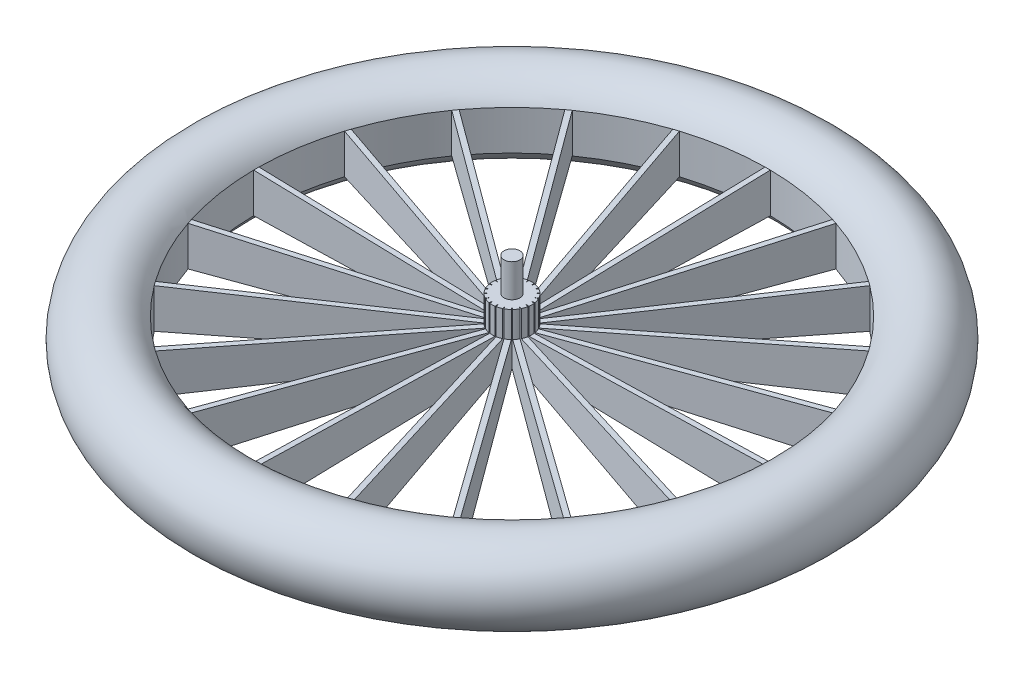
SolidWorks part; units mm, degrees
ref_plane "Plan de face" through (0, 0, 0) normal (0, 0, 1) x (1, 0, 0)
ref_plane "Plan de dessus" through (0, 0, 0) normal (0, 1, 0) x (1, 0, 0)
ref_plane "Plan de droite" through (0, 0, 0) normal (1, 0, 0) x (0, 0, -1)
sketch "Esquisse1" plane through (0, 0, 0) normal (0, 0, 1) x (1, 0, 0)
  line L0 (0, 0) -> (50000, 0) construction
  line L1 (-6, -30) -> (6, -30)
  line L2 (-6, -30) -> (-6, 30)
  line L3 (-6, 30) -> (6, 30)
  line L4 (6, -30) -> (6, 30)
  line L5 (-6, -30) -> (6, 30) construction
  line L6 (-6, 30) -> (6, -30) construction
  line L7 (-194.0192, 15) -> (-6, 10)
  line L8 (-6, -10) -> (6, -10)
  line L9 (-6, -10) -> (-6, 10)
  line L10 (-6, 10) -> (6, 10)
  line L11 (6, -10) -> (6, 10)
  line L12 (-6, -10) -> (6, 10) construction
  line L13 (-6, 10) -> (6, -10) construction
  line L14 (-220, -30) -> (220, -30)
  line L15 (-220, -30) -> (-220, 30)
  line L16 (-220, 30) -> (220, 30)
  line L17 (220, -30) -> (220, 30)
  line L18 (-220, -30) -> (220, 30) construction
  line L19 (-220, 30) -> (220, -30) construction
  line L20 (-245.9808, -15) -> (-194.0192, -15)
  line L21 (-245.9808, -15) -> (-245.9808, 15)
  line L22 (-245.9808, 15) -> (-194.0192, 15)
  line L23 (0, 30) -> (0, -30)
  line L24 (-194.0192, -15) -> (-194.0192, 15)
  line L25 (-15, 30) -> (15, 30)
  line L26 (-15, 30) -> (-15, -30)
  line L27 (-15, -30) -> (15, -30)
  line L28 (15, 30) -> (15, -30)
  line L29 (-15, 30) -> (15, -30) construction
  line L30 (-15, -30) -> (15, 30) construction
  line L31 (-245.9808, -15) -> (-194.0192, 15) construction
  line L32 (-245.9808, 15) -> (-194.0192, -15) construction
  line L33 (-194.0192, -15) -> (-6, -10)
  line L34 (0, 55) -> (0, -55)
  line L35 (-6, -55) -> (6, -55)
  line L36 (-6, -55) -> (-6, 55)
  line L37 (-6, 55) -> (6, 55)
  line L38 (6, -55) -> (6, 55)
  line L39 (-6, -55) -> (6, 55) construction
  line L40 (-6, 55) -> (6, -55) construction
  circle A0 centre (220, 0) radius 30
  circle A1 centre (-220, 0) radius 30
  point P0 (0, 0)
  point P8 (6, 0)
  point P9 (0, 0)
  point P14 (0, 0)
  point P25 (0, 0)
  point P34 (0, 0)
  dimension "D1" = 12
  dimension "D2" = 60
  dimension "D3" = 20
  dimension "D4" = 60
  dimension "D5" = 440
  dimension "D6" = 30
  dimension "D7" = 30
  dimension "D8" = 12
  dimension "D9" = 110
revolve "Révolution1" add sketch "Esquisse1" angle 360 about L23 region at (-10.5177, 0, 0) region at (-10.491, 20.0597, 0) region at (-3, 20, 0) region at (-108.6258, 0, 0) region at (-230.1761, -21.1506, 0) region at (-209.8239, -21.1506, 0) region at (-3, 42.5, 0) region at (-207.0096, 0, 0) region at (-192.4019, 0, 0) region at (-232.9904, 0, 0) region at (-247.5981, 0, 0) region at (-209.8239, 21.1506, 0) region at (-230.1761, 21.1506, 0)
sketch "Esquisse4" plane through (0, 0, 0) normal (0, 1, 0) x (1, 0, 0)
  line L0 (0, 194.0192) -> (0, 15)
  line L1 (0, 15) -> (0, 0)
  line L2 (-2, 194.0192) -> (-2, 15)
  line L3 (-2, 15) -> (-2, 0)
  line L4 (2, 194.0192) -> (2, 15)
  line L5 (2, 15) -> (2, 0)
  line L6 (58.0531, 185.1413) -> (2.7331, 14.8839)
  line L7 (61.8574, 183.9052) -> (6.5374, 13.6478)
  line L8 (2.7331, 14.8839) -> (-1.9021, 0.618)
  line L9 (6.5374, 13.6478) -> (1.9021, -0.618)
  line L10 (112.4236, 158.1404) -> (7.1987, 13.3108)
  line L11 (115.6597, 155.7893) -> (10.4348, 10.9597)
  line L12 (7.1987, 13.3108) -> (-1.618, 1.1756)
  line L13 (10.4348, 10.9597) -> (1.618, -1.1756)
  line L14 (155.7893, 115.6597) -> (10.9597, 10.4348)
  line L15 (158.1404, 112.4236) -> (13.3108, 7.1987)
  line L16 (10.9597, 10.4348) -> (-1.1756, 1.618)
  line L17 (13.3108, 7.1987) -> (1.1756, -1.618)
  line L18 (183.9052, 61.8574) -> (13.6478, 6.5374)
  line L19 (185.1413, 58.0531) -> (14.8839, 2.7331)
  line L20 (13.6478, 6.5374) -> (-0.618, 1.9021)
  line L21 (14.8839, 2.7331) -> (0.618, -1.9021)
  line L22 (194.0192, 2) -> (15, 2)
  line L23 (194.0192, -2) -> (15, -2)
  line L24 (15, 2) -> (0, 2)
  line L25 (15, -2) -> (0, -2)
  line L26 (185.1413, -58.0531) -> (14.8839, -2.7331)
  line L27 (183.9052, -61.8574) -> (13.6478, -6.5374)
  line L28 (14.8839, -2.7331) -> (0.618, 1.9021)
  line L29 (13.6478, -6.5374) -> (-0.618, -1.9021)
  line L30 (158.1404, -112.4236) -> (13.3108, -7.1987)
  line L31 (155.7893, -115.6597) -> (10.9597, -10.4348)
  line L32 (13.3108, -7.1987) -> (1.1756, 1.618)
  line L33 (10.9597, -10.4348) -> (-1.1756, -1.618)
  line L34 (115.6597, -155.7893) -> (10.4348, -10.9597)
  line L35 (112.4236, -158.1404) -> (7.1987, -13.3108)
  line L36 (10.4348, -10.9597) -> (1.618, 1.1756)
  line L37 (7.1987, -13.3108) -> (-1.618, -1.1756)
  line L38 (61.8574, -183.9052) -> (6.5374, -13.6478)
  line L39 (58.0531, -185.1413) -> (2.7331, -14.8839)
  line L40 (6.5374, -13.6478) -> (1.9021, 0.618)
  line L41 (2.7331, -14.8839) -> (-1.9021, -0.618)
  line L42 (2, -194.0192) -> (2, -15)
  line L43 (-2, -194.0192) -> (-2, -15)
  line L44 (2, -15) -> (2, 0)
  line L45 (-2, -15) -> (-2, 0)
  line L46 (-58.0531, -185.1413) -> (-2.7331, -14.8839)
  line L47 (-61.8574, -183.9052) -> (-6.5374, -13.6478)
  line L48 (-2.7331, -14.8839) -> (1.9021, -0.618)
  line L49 (-6.5374, -13.6478) -> (-1.9021, 0.618)
  line L50 (-112.4236, -158.1404) -> (-7.1987, -13.3108)
  line L51 (-115.6597, -155.7893) -> (-10.4348, -10.9597)
  line L52 (-7.1987, -13.3108) -> (1.618, -1.1756)
  line L53 (-10.4348, -10.9597) -> (-1.618, 1.1756)
  line L54 (-155.7893, -115.6597) -> (-10.9597, -10.4348)
  line L55 (-158.1404, -112.4236) -> (-13.3108, -7.1987)
  line L56 (-10.9597, -10.4348) -> (1.1756, -1.618)
  line L57 (-13.3108, -7.1987) -> (-1.1756, 1.618)
  line L58 (-183.9052, -61.8574) -> (-13.6478, -6.5374)
  line L59 (-185.1413, -58.0531) -> (-14.8839, -2.7331)
  line L60 (-13.6478, -6.5374) -> (0.618, -1.9021)
  line L61 (-14.8839, -2.7331) -> (-0.618, 1.9021)
  line L62 (-194.0192, -2) -> (-15, -2)
  line L63 (-194.0192, 2) -> (-15, 2)
  line L64 (-15, -2) -> (0, -2)
  line L65 (-15, 2) -> (0, 2)
  line L66 (-185.1413, 58.0531) -> (-14.8839, 2.7331)
  line L67 (-183.9052, 61.8574) -> (-13.6478, 6.5374)
  line L68 (-14.8839, 2.7331) -> (-0.618, -1.9021)
  line L69 (-13.6478, 6.5374) -> (0.618, 1.9021)
  line L70 (-158.1404, 112.4236) -> (-13.3108, 7.1987)
  line L71 (-155.7893, 115.6597) -> (-10.9597, 10.4348)
  line L72 (-13.3108, 7.1987) -> (-1.1756, -1.618)
  line L73 (-10.9597, 10.4348) -> (1.1756, 1.618)
  line L74 (-115.6597, 155.7893) -> (-10.4348, 10.9597)
  line L75 (-112.4236, 158.1404) -> (-7.1987, 13.3108)
  line L76 (-10.4348, 10.9597) -> (-1.618, -1.1756)
  line L77 (-7.1987, 13.3108) -> (1.618, 1.1756)
  line L78 (-61.8574, 183.9052) -> (-6.5374, 13.6478)
  line L79 (-58.0531, 185.1413) -> (-2.7331, 14.8839)
  line L80 (-6.5374, 13.6478) -> (-1.9021, -0.618)
  line L81 (-2.7331, 14.8839) -> (1.9021, 0.618)
  circle A0 centre (0, 0) radius 15 construction
  circle A1 centre (0, 0) radius 194.0192
  circle A2 centre (0, 0) radius 194.0192
  point P131 (0, 0)
  dimension "D2" = 2
  dimension "D1" = 0
  dimension "D3" = 2
  dimension "D4" = 20
extrude "Enlèv. mat.-Extru.2" cut sketch "Esquisse4" against normal through all both and the other way through all contours L2 A2 L79 L81 L3 | L78 A2 L75 L77 L80 | L74 A2 L71 L73 L76 | L70 A2 L67 L69 L72 | L66 A2 L63 L65 L68 | L62 A2 L59 L61 L64 | L58 A2 L55 L57 L60 | L54 A2 L51 L53 L56 | L50 A2 L47 L49 L52 | L46 A2 L43 L45 L48 | L42 A2 L39 L41 L44 | L38 A2 L35 L37 L40 | L34 A2 L31 L33 L36 | L30 A2 L27 L29 L32 | L26 A2 L23 L25 L28 | L22 A2 L19 L21 L24 | L18 A2 L15 L17 L20 | L14 A2 L11 L13 L16 | L10 A2 L7 L9 L12 | L6 A2 L4 L5 L8 region at (20.8283, 0, -131.5046) region at (-20.8283, 0, -131.5046) region at (60.446, 0, -118.632) region at (-60.446, 0, -118.632) region at (94.1469, 0, -94.1469) region at (-94.1469, 0, -94.1469) region at (118.632, 0, -60.446) region at (-118.632, 0, -60.446) region at (131.5046, 0, -20.8283) region at (-131.5046, 0, -20.8283) region at (-131.5046, 0, 20.8283) region at (131.5046, 0, 20.8283) region at (-118.632, 0, 60.446) region at (118.632, 0, 60.446) region at (-94.1469, 0, 94.1469) region at (94.1469, 0, 94.1469) region at (-60.446, 0, 118.632) region at (60.446, 0, 118.632) region at (-20.8283, 0, 131.5046) region at (20.8283, 0, 131.5046)
